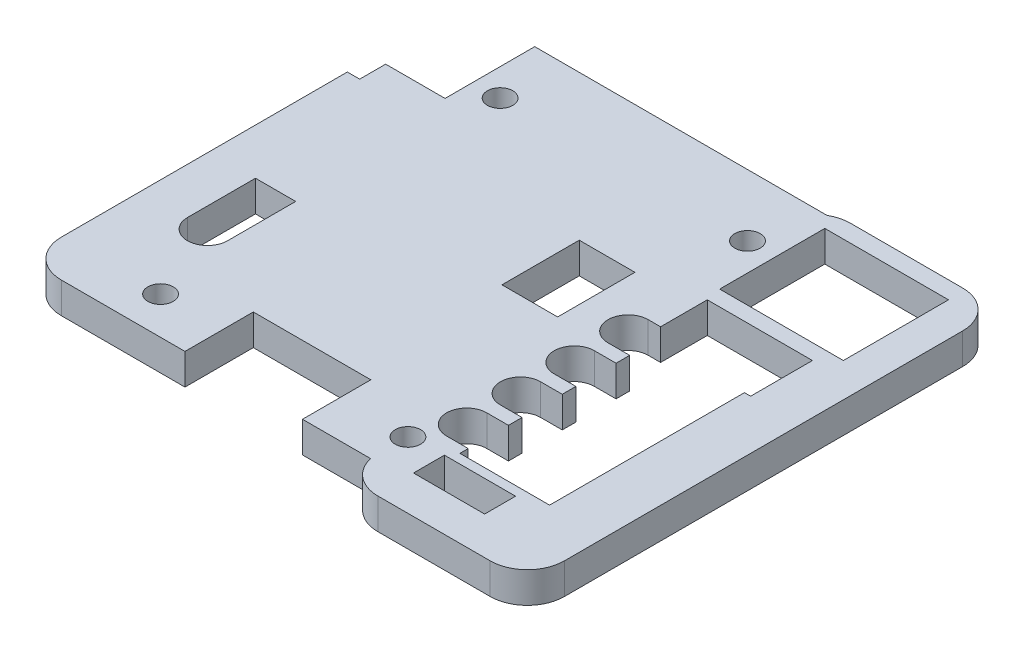
SolidWorks part; units mm, degrees
ref_plane "前视基准面" through (0, 0, 0) normal (0, 0, 1) x (1, 0, 0)
ref_plane "上视基准面" through (0, 0, 0) normal (0, 1, 0) x (1, 0, 0)
ref_plane "右视基准面" through (0, 0, 0) normal (1, 0, 0) x (0, 0, -1)
sketch "草图1" plane through (0, 0, 0) normal (0, 1, 0) x (1, 0, 0)
  line L0 (6, 0.3) -> (143.8, 0.3)
  line L1 (6, 0) -> (143.8, 0) construction
  line L2 (0, -6) -> (0, -68.8) construction
  line L3 (6, -74.8) -> (143.8, -74.8) construction
  line L4 (149.8, -6) -> (149.8, -68.8) construction
  line L5 (150.1, -6) -> (150.1, -68.8)
  line L6 (6, -75.1) -> (143.8, -75.1)
  line L7 (-0.3, -6) -> (-0.3, -68.8)
  arc A0 (143.8, 0) -> (149.8, -6) centre (143.8, -6) cw construction
  arc A1 (143.8, -74.8) -> (149.8, -68.8) centre (143.8, -68.8) ccw construction
  arc A2 (0, -68.8) -> (6, -74.8) centre (6, -68.8) ccw construction
  arc A3 (6, 0) -> (0, -6) centre (6, -6) ccw construction
  arc A4 (143.8, 0.3) -> (150.1, -6) centre (143.8, -6) cw
  arc A5 (143.8, -75.1) -> (150.1, -68.8) centre (143.8, -68.8) ccw
  arc A6 (-0.3, -68.8) -> (6, -75.1) centre (6, -68.8) ccw
  arc A7 (6, 0.3) -> (-0.3, -6) centre (6, -6) ccw
  point P7 (149.8, 0)
  point P12 (0, -74.8)
  point P15 (0, 0)
  dimension "D3" = 6
  dimension "D1" = 74.8
  dimension "D2" = 149.8
  dimension "D4" = 0.3
sketch "草图2" plane through (0, 0, 0) normal (0, -1, 0) x (-1, 0, 0)
  line L0 (-122.6, -55.35) -> (-108.9, -55.35) construction
  line L1 (-122.6, -69.85) -> (-108.9, -69.85) construction
  line L2 (-122.6, -69.85) -> (-122.6, -63.95) construction
  line L3 (-122.6, -63.95) -> (-108.9, -63.95) construction
  line L4 (-108.9, -69.85) -> (-108.9, -63.95) construction
  line L5 (-135.3, -1.25) -> (-35.3, -1.25) construction
  line L6 (-135.3, -1.25) -> (-135.3, -73.55) construction
  line L7 (-135.3, -73.55) -> (-35.3, -73.55) construction
  line L8 (-35.3, -1.25) -> (-35.3, -73.55) construction
  line L9 (-108.9, -61.25) -> (-108.9, -55.35) construction
  line L10 (-122.6, -61.25) -> (-108.9, -61.25) construction
  line L11 (-122.6, -61.25) -> (-122.6, -55.35) construction
  line L12 (-122.6, -46.75) -> (-108.9, -46.75) construction
  line L13 (-108.9, -52.65) -> (-108.9, -46.75) construction
  line L14 (-122.6, -52.65) -> (-108.9, -52.65) construction
  line L15 (-122.6, -52.65) -> (-122.6, -46.75) construction
  line L16 (-122.6, -38.15) -> (-108.9, -38.15) construction
  line L17 (-108.9, -44.05) -> (-108.9, -38.15) construction
  line L18 (-122.6, -44.05) -> (-108.9, -44.05) construction
  line L19 (-122.6, -44.05) -> (-122.6, -38.15) construction
  line L20 (0, -6) -> (0, -68.8) construction
  line L21 (-35.3, -73.55) -> (-0.8, -73.55) construction
  line L22 (-120.25, -26.65) -> (-111.25, -26.65) construction
  line L23 (-120.25, -26.65) -> (-120.25, -33.15) construction
  line L24 (-120.25, -33.15) -> (-111.25, -33.15) construction
  line L25 (-111.25, -26.65) -> (-111.25, -33.15) construction
  line L26 (-85.8, -48.75) -> (-81.1, -48.75) construction
  line L27 (-85.8, -48.75) -> (-85.8, -58.15) construction
  line L28 (-85.8, -58.15) -> (-81.1, -58.15) construction
  line L29 (-81.1, -48.75) -> (-81.1, -58.15) construction
  line L30 (-71.5, -48.65) -> (-68.2, -48.65) construction
  line L31 (-71.5, -48.65) -> (-71.5, -57.55) construction
  line L32 (-71.5, -57.55) -> (-68.2, -57.55) construction
  line L33 (-68.2, -48.65) -> (-68.2, -57.55) construction
  line L34 (-43.1, -45.05) -> (-38.6, -45.05) construction
  line L35 (-43.1, -45.05) -> (-43.1, -59.05) construction
  line L36 (-43.1, -59.05) -> (-38.6, -59.05) construction
  line L37 (-38.6, -45.05) -> (-38.6, -59.05) construction
  line L38 (-45.3, -61.55) -> (-40.8, -61.55) construction
  line L39 (-45.3, -61.55) -> (-45.3, -66.05) construction
  line L40 (-45.3, -66.05) -> (-40.8, -66.05) construction
  line L41 (-40.8, -61.55) -> (-40.8, -66.05) construction
  line L42 (-0.8, -73.55) -> (-0.8, -1.25) construction
  line L43 (-0.8, -1.25) -> (-35.3, -1.25) construction
  line L44 (-149.8, -6) -> (-149.8, -68.8) construction
  line L45 (-30.8, -34.65) -> (-27.3, -34.65) construction
  line L46 (-30.8, -34.65) -> (-30.8, -40.15) construction
  line L47 (-30.8, -40.15) -> (-27.3, -40.15) construction
  line L48 (-27.3, -34.65) -> (-27.3, -40.15) construction
  line L49 (-120.75, -33.65) -> (-110.75, -33.65)
  line L50 (-110.75, -26.15) -> (-110.75, -33.65)
  line L51 (-120.75, -26.15) -> (-110.75, -26.15)
  line L52 (-120.75, -26.15) -> (-120.75, -33.65)
  line L53 (-86.3, -48.25) -> (-86.3, -58.65)
  line L54 (-86.3, -58.65) -> (-80.6, -58.65)
  line L55 (-80.6, -48.25) -> (-80.6, -58.65)
  line L56 (-86.3, -48.25) -> (-80.6, -48.25)
  line L57 (-72, -48.15) -> (-72, -58.05)
  line L58 (-72, -58.05) -> (-67.7, -58.05)
  line L59 (-67.7, -48.15) -> (-67.7, -58.05)
  line L60 (-72, -48.15) -> (-67.7, -48.15)
  line L61 (-31.3, -34.15) -> (-31.3, -40.65)
  line L62 (-31.3, -40.65) -> (-26.8, -40.65)
  line L63 (-26.8, -34.15) -> (-26.8, -40.65)
  line L64 (-31.3, -34.15) -> (-26.8, -34.15)
  line L65 (-43.6, -44.55) -> (-43.6, -59.55)
  line L66 (-43.6, -59.55) -> (-38.1, -59.55)
  line L67 (-38.1, -44.55) -> (-38.1, -59.55)
  line L68 (-43.6, -44.55) -> (-38.1, -44.55)
  line L69 (-45.8, -61.05) -> (-45.8, -66.55)
  line L70 (-45.8, -66.55) -> (-40.3, -66.55)
  line L71 (-40.3, -61.05) -> (-40.3, -66.55)
  line L72 (-45.8, -61.05) -> (-40.3, -61.05)
  line L73 (-122.9, -44.35) -> (-108.6, -44.35)
  line L74 (-108.6, -44.35) -> (-108.6, -37.85)
  line L75 (-122.9, -37.85) -> (-108.6, -37.85)
  line L76 (-122.9, -44.35) -> (-122.9, -37.85)
  line L77 (-122.9, -52.95) -> (-108.6, -52.95)
  line L78 (-108.6, -52.95) -> (-108.6, -46.45)
  line L79 (-122.9, -46.45) -> (-108.6, -46.45)
  line L80 (-122.9, -52.95) -> (-122.9, -46.45)
  line L81 (-122.9, -61.55) -> (-108.6, -61.55)
  line L82 (-108.6, -61.55) -> (-108.6, -55.05)
  line L83 (-122.9, -55.05) -> (-108.6, -55.05)
  line L84 (-122.9, -61.55) -> (-122.9, -55.05)
  line L85 (-122.9, -70.15) -> (-108.6, -70.15)
  line L86 (-108.6, -70.15) -> (-108.6, -63.65)
  line L87 (-122.9, -63.65) -> (-108.6, -63.65)
  line L88 (-122.9, -70.15) -> (-122.9, -63.65)
  circle A0 centre (-103.2, -9.35) radius 1.65 construction
  circle A1 centre (-103.2, -64.25) radius 1.65 construction
  circle A2 centre (-63.2, -64.25) radius 1.65 construction
  circle A3 centre (-63.2, -9.35) radius 1.65 construction
  circle A4 centre (-130.8, -5.6) radius 1.25 construction
  circle A5 centre (-131.1, -55.65) radius 1.25 construction
  circle A6 centre (-47.7, -4.85) radius 1.25 construction
  circle A7 centre (-48.1, -68.75) radius 1.25 construction
  circle A8 centre (-22.8, -70.3) radius 1.25 construction
  circle A9 centre (-5.05, -71.05) radius 1.25 construction
  circle A10 centre (-5.05, -3.25) radius 1.25 construction
  circle A11 centre (-19, -37.4) radius 3.6 construction
  circle A12 centre (-103.2, -9.35) radius 2.05
  circle A13 centre (-63.2, -9.35) radius 2.05
  circle A14 centre (-63.2, -64.25) radius 2.05
  circle A15 centre (-103.2, -64.25) radius 2.05
  circle A16 centre (-19, -37.4) radius 4.1
  circle A17 centre (-130.8, -5.6) radius 1.75
  circle A18 centre (-131.1, -55.65) radius 1.75
  circle A19 centre (-48.1, -68.75) radius 1.75
  circle A20 centre (-22.8, -70.3) radius 1.75
  circle A21 centre (-5.05, -71.05) radius 1.75
  circle A22 centre (-5.05, -3.25) radius 1.75
  circle A23 centre (-47.7, -4.85) radius 1.75
  point P22 (0, -37.4)
  point P23 (-135.3, -37.4)
  point P28 (-115.75, -33.15)
  point P29 (-115.75, -38.15)
  point P30 (-111.25, -29.9)
  point P31 (-108.9, -41.1)
  point P79 (-0.8, -37.4)
  point P81 (-27.3, -37.4)
  dimension "D21" = 3.3
  dimension "D34" = 2.5
  dimension "D53" = 7.2
  dimension "D1" = 13.7
  dimension "D2" = 5.9
  dimension "D3" = 72.3
  dimension "D4" = 3.7
  dimension "D5" = 12.7
  dimension "D7" = 14.5
  dimension "D8" = 100
  dimension "D9" = 2.7
  dimension "D10" = 9
  dimension "D11" = 6.5
  dimension "D12" = 11.2
  dimension "D13" = 15.4
  dimension "D14" = 9.4
  dimension "D15" = 4.7
  dimension "D16" = 23.1
  dimension "D17" = 3.3
  dimension "D18" = 8.9
  dimension "D19" = 16
  dimension "D20" = 37.4
  dimension "D22" = 8.1
  dimension "D23" = 32.1
  dimension "D24" = 40
  dimension "D25" = 9.3
  dimension "D26" = 14
  dimension "D27" = 4.5
  dimension "D28" = 4.5
  dimension "D29" = 4.5
  dimension "D30" = 3.3
  dimension "D31" = 5.5
  dimension "D32" = 7.5
  dimension "D33" = 14.5
  dimension "D35" = 34.5
  dimension "D36" = 2
  dimension "D37" = 4.25
  dimension "D38" = 2.5
  dimension "D39" = 3.25
  dimension "D40" = 22
  dimension "D41" = 4.8
  dimension "D42" = 12.8
  dimension "D43" = 3.6
  dimension "D44" = 12.4
  dimension "D45" = 4.35
  dimension "D46" = 4.5
  dimension "D47" = 4.2
  dimension "D48" = 17.9
  dimension "D49" = 18.2
  dimension "D50" = 3.5
  dimension "D51" = 5.5
  dimension "D52" = 8.3
  dimension "D54" = 0.4
  dimension "D55" = 0.5
  dimension "D56" = 0.5
  dimension "D57" = 0.5
  dimension "D58" = 0.3
  dimension "D6" = 4
sketch "草图3" plane through (0, 0, 0) normal (0, 1, 0) x (1, 0, 0)
  line L0 (135.3, -1.25) -> (135.3, -73.55) construction
  line L1 (143.8, 0) -> (135.3, 0)
  line L2 (149.8, -6) -> (149.8, -68.8)
  line L3 (143.8, -74.8) -> (135.3, -74.8)
  line L4 (135.3, 0) -> (135.3, -74.8)
  line L5 (6, -74.8) -> (143.8, -74.8) construction
  arc A0 (143.8, 0) -> (149.8, -6) centre (143.8, -6) cw
  arc A1 (149.8, -68.8) -> (143.8, -74.8) centre (143.8, -68.8) cw
  point P17 (149.8, 0)
  dimension "D1" = 6
sketch "草图4" plane through (0, 0, 0) normal (0, 1, 0) x (1, 0, 0)
  line L0 (122.9, -62.85) -> (108.6, -62.85)
  line L1 (122.6, -63.15) -> (108.9, -63.15) construction
  line L2 (122.6, -63.15) -> (122.6, -70.65) construction
  line L3 (122.6, -70.65) -> (108.9, -70.65) construction
  line L4 (108.9, -63.15) -> (108.9, -70.65) construction
  line L5 (122.6, -69.85) -> (122.6, -63.95) construction
  line L6 (108.6, -62.85) -> (108.6, -70.95)
  line L7 (108.9, -69.85) -> (108.9, -63.95) construction
  line L8 (122.6, -54.55) -> (108.9, -54.55) construction
  line L9 (108.9, -54.55) -> (108.9, -62.05) construction
  line L10 (122.6, -62.05) -> (108.9, -62.05) construction
  line L11 (122.6, -54.55) -> (122.6, -62.05) construction
  line L12 (122.6, -45.95) -> (108.9, -45.95) construction
  line L13 (108.9, -45.95) -> (108.9, -53.45) construction
  line L14 (122.6, -53.45) -> (108.9, -53.45) construction
  line L15 (122.6, -45.95) -> (122.6, -53.45) construction
  line L16 (122.6, -37.35) -> (108.9, -37.35) construction
  line L17 (108.9, -37.35) -> (108.9, -44.85) construction
  line L18 (122.6, -44.85) -> (108.9, -44.85) construction
  line L19 (122.6, -37.35) -> (122.6, -44.85) construction
  line L20 (122.9, -70.95) -> (108.6, -70.95)
  line L21 (122.9, -62.85) -> (122.9, -70.95)
  line L22 (122.9, -54.25) -> (108.6, -54.25)
  line L23 (108.6, -54.25) -> (108.6, -62.35)
  line L24 (122.9, -62.35) -> (108.6, -62.35)
  line L25 (122.9, -54.25) -> (122.9, -62.35)
  line L26 (122.9, -45.65) -> (108.6, -45.65)
  line L27 (108.6, -45.65) -> (108.6, -53.75)
  line L28 (122.9, -53.75) -> (108.6, -53.75)
  line L29 (122.9, -45.65) -> (122.9, -53.75)
  line L30 (122.9, -37.05) -> (108.6, -37.05)
  line L31 (108.6, -37.05) -> (108.6, -45.15)
  line L32 (122.9, -45.15) -> (108.6, -45.15)
  line L33 (122.9, -37.05) -> (122.9, -45.15)
  point P11 (108.9, -66.9)
  point P12 (108.9, -66.9)
  dimension "D1" = 7.5
  dimension "D3" = 1.1
  dimension "D4" = 0.3
  dimension "D2" = 4
extrude "拉伸-薄壁1" add sketch "草图2" along normal blind 5 thin contours A13 | A12 | A14 | A15 thin type one direction wall 4
sketch "草图6" plane through (0, 0, 0) normal (0, 1, 0) x (1, 0, 0)
  line L0 (127.2, 1.45) -> (109.0462, 1.45)
  line L1 (133.2, -4.55) -> (133.2, -68.95)
  line L2 (127.2, -74.95) -> (109.0462, -74.95)
  line L3 (33.4345, -36.75) -> (43.3021, -36.75) construction
  line L4 (63.2, 0.65) -> (106.0528, 0.65)
  line L6 (63.2, 0.65) -> (49.7, 0.65)
  line L10 (122.9, -70.95) -> (108.6, -70.95) construction
  line L11 (108.6, -62.85) -> (108.6, -70.95) construction
  line L12 (47.2, -1.85) -> (47.2, -64.3)
  line L13 (103.2, -70.3) -> (53.2, -70.3)
  circle A1 centre (103.2, -64.25) radius 6.05 construction
  arc A3 (133.2, -4.55) -> (127.2, 1.45) centre (127.2, -4.55) ccw
  arc A4 (109.0462, -74.95) -> (103.2, -70.3) centre (109.0462, -68.95) cw
  circle A5 centre (63.2, -64.25) radius 6.05 construction
  arc A6 (133.2, -68.95) -> (127.2, -74.95) centre (127.2, -68.95) cw
  arc A7 (109.0462, 1.45) -> (106.0528, 0.65) centre (109.0462, -4.55) ccw
  arc A9 (47.2, -64.3) -> (53.2, -70.3) centre (53.2, -64.3) ccw
  circle A10 centre (103.2, -9.35) radius 2.05 construction
  circle A11 centre (103.2, -64.25) radius 2.05 construction
  circle A12 centre (63.2, -64.25) radius 2.05 construction
  circle A13 centre (103.2, -9.35) radius 2.05
  circle A14 centre (103.2, -64.25) radius 2.05
  circle A15 centre (63.2, -64.25) radius 2.05
  circle A16 centre (63.2, -9.35) radius 2.05 construction
  circle A17 centre (63.2, -9.35) radius 2.05
  arc A18 (49.7, 0.65) -> (47.2, -1.85) centre (49.7, -1.85) ccw
  point P37 (105.6, -74.95)
  point P42 (130.9, -6.15)
  dimension "D6" = 6
  dimension "D7" = 5
  dimension "D8" = 6
  dimension "D9" = 6
  dimension "D10" = 6
  dimension "D11" = 6
  dimension "D2" = 27.5
  dimension "D3" = 4
  dimension "D4" = 3
  dimension "D5" = 16
  dimension "D12" = 30
  dimension "D13" = 10
extrude "凸台-拉伸1" add sketch "草图6" against normal up to surface (5 mm away) up to face at (97.15, -5, 9.35)
sketch "草图7" plane through (0, -5, 3) normal (0, -1, 0) x (1, 0, 0)
  line L9 (80.466, 15.85) -> (96.6871, 15.85) construction
  line L43 (107.2, -14.628) -> (107.2, -27.7853) construction
  line L44 (108.9, 22) -> (108.9, 67) construction
  line L45 (122.6, 67) -> (108.9, 67) construction
  line L46 (122.6, 22) -> (122.6, 67) construction
  line L47 (122.6, 22) -> (108.9, 22) construction
  line L48 (120.2, 9.55) -> (113.2, 9.55)
  line L49 (120.2, 4.55) -> (120.2, 9.55)
  line L50 (113.2, 4.55) -> (120.2, 4.55)
  line L51 (113.2, 9.55) -> (113.2, 4.55)
  line L52 (80.4, 48.65) -> (80.4, 33.65)
  line L53 (85.4, 48.65) -> (80.4, 48.65)
  line L54 (97.9, 36.55) -> (89.9, 36.55)
  line L55 (97.9, 25.55) -> (97.9, 36.55)
  line L56 (89.9, 25.55) -> (97.9, 25.55)
  line L57 (89.9, 36.55) -> (89.9, 25.55)
  line L58 (66.4, 33.65) -> (80.4, 33.65)
  line L59 (50.4, 54.65) -> (50.4, 33.65)
  line L60 (85.4, 54.65) -> (50.4, 54.65)
  line L61 (85.4, 48.65) -> (85.4, 54.65)
  line L62 (47.4, 10.15) -> (66.4, 10.15)
  line L63 (47.4, 33.65) -> (47.4, 10.15)
  line L64 (50.4, 33.65) -> (47.4, 33.65)
  line L65 (66.4, 10.15) -> (66.4, 15.35)
  line L66 (66.4, 24.35) -> (72.4, 24.35)
  line L67 (66.4, 24.35) -> (66.4, 33.65)
  line L68 (72.4, 15.35) -> (66.4, 15.35)
  line L69 (122.9, 21.7) -> (122.9, 67.3)
  line L70 (122.9, 67.3) -> (108.6, 67.3)
  line L71 (72.4, 24.35) -> (72.4, 15.35)
  line L72 (92.2, 15.35) -> (75.2, 15.35)
  line L73 (92.2, 23.55) -> (92.2, 15.35)
  line L74 (75.2, 23.55) -> (92.2, 23.55)
  line L75 (107.7, 23.55) -> (107.7, 15.35)
  line L76 (98.2, 23.55) -> (107.7, 23.55)
  line L77 (98.2, 15.35) -> (98.2, 23.55)
  line L78 (107.7, 15.35) -> (98.2, 15.35)
  line L79 (75.2, 15.35) -> (75.2, 23.55)
  line L80 (108.6, 21.7) -> (108.6, 67.3)
  line L81 (122.9, 21.7) -> (108.6, 21.7)
  circle A0 centre (103.2, 61.25) radius 2.05 construction
  circle A1 centre (103.2, 61.25) radius 2.05
  circle A5 centre (59.2, 61.25) radius 2.05
  circle A6 centre (103.2, 61.25) radius 2.05
extrude "切除-拉伸1" [suppressed] cut sketch "草图7" against normal blind 5 contours L81 L69 L70 L80 | L78 L75 L76 L77 | L54 L57 L56 L55 | L79 L72 L73 L74 | L71 L66 L67 L58 L52 L53 L61 L60 L59 L64 L63 L62 L65 L68
sketch "草图8" plane through (0, 0, 0) normal (0, -1, 0) x (1, 0, 0)
  line L3 (106.2, 28.95) -> (106.2, 55.65) construction
  line L6 (133.2, 68.95) -> (133.2, 4.55) construction
  line L7 (109.0462, 74.95) -> (127.2, 74.95) construction
  line L9 (80.466, -18.85) -> (96.6871, -18.85) construction
  line L10 (107.2, 11.628) -> (107.2, 24.7853) construction
  line L14 (5.1637, 36.85) -> (19.0276, 36.85) construction
  line L15 (106.2, 60.7) -> (109.7, 60.7)
  line L18 (63.2, 64.25) -> (46.0308, 64.25) construction
  line L19 (67.2, 40.45) -> (49.2, 40.45)
  line L20 (106.2, 54.2) -> (109.7, 54.2)
  line L22 (67.2, 13.45) -> (67.2, 40.45)
  line L23 (49.2, 13.45) -> (67.2, 13.45)
  line L24 (49.2, 40.45) -> (49.2, 13.45)
  line L25 (98.5, 35.95) -> (89.5, 35.95)
  line L26 (98.5, 23.45) -> (98.5, 35.95)
  line L27 (89.5, 23.45) -> (98.5, 23.45)
  line L28 (89.5, 35.95) -> (89.5, 23.45)
  line L29 (108.2, 30.95) -> (125.2, 30.95) construction
  line L30 (128.2, 18.45) -> (108.2, 18.45)
  line L31 (128.2, 2.45) -> (128.2, 18.45)
  line L32 (108.2, 2.45) -> (128.2, 2.45)
  line L37 (108.2, 18.45) -> (108.2, 2.45)
  line L38 (125.2, 20.95) -> (125.2, 30.95)
  line L47 (125.2, 30.95) -> (124.2, 30.95)
  line L48 (108.2, 30.95) -> (108.2, 20.95)
  line L49 (108.2, 30.95) -> (109.7, 30.95)
  line L50 (125.2, 20.95) -> (108.2, 20.95)
  line L51 (111.7, 64.75) -> (122.2, 64.75)
  line L52 (122.2, 62.75) -> (122.2, 69.95)
  line L53 (124.2, 30.95) -> (124.2, 63.75)
  line L54 (109.7, 63.75) -> (124.2, 63.75)
  line L55 (111.7, 69.95) -> (122.2, 69.95)
  line L56 (111.7, 69.95) -> (111.7, 62.75)
  line L57 (109.7, 30.95) -> (109.7, 63.75)
  line L58 (75.2, 64.35) -> (89.2, 64.35)
  line L59 (75.2, 73.35) -> (75.2, 64.35)
  line L60 (89.2, 73.35) -> (75.2, 73.35)
  line L61 (89.2, 64.35) -> (89.2, 73.35)
  line L62 (106.2, 51.8) -> (109.7, 51.8)
  line L63 (106.2, 45.3) -> (109.7, 45.3)
  line L64 (106.2, 42.9) -> (109.7, 42.9)
  line L65 (106.2, 36.4) -> (109.7, 36.4)
  line L66 (106.2, 34) -> (109.7, 34)
  line L67 (106.2, 27.5) -> (108.2, 27.5)
  line L68 (109.7, 34) -> (109.7, 27.5)
  line L69 (109.7, 27.5) -> (108.2, 27.5)
  line L70 (109.7, 36.4) -> (109.7, 42.9)
  line L71 (109.7, 45.3) -> (109.7, 51.8)
  line L72 (109.7, 54.2) -> (109.7, 60.7)
  circle A1 centre (57.9, 42.45) radius 3.25
  circle A2 centre (103.2, 9.35) radius 2.4
  circle A3 centre (106.2, 57.45) radius 3.25
  circle A4 centre (63.2, 9.35) radius 2.4
  circle A5 centre (103.2, 64.25) radius 2.4 construction
  circle A10 centre (106.2, 48.55) radius 3.25
  circle A11 centre (63.2, 64.25) radius 2.4 construction
  circle A14 centre (106.2, 39.65) radius 3.25
  circle A15 centre (106.2, 30.75) radius 3.25
  dimension "D7" = 27.5
  dimension "D1" = 10
  dimension "D3" = 8.9
  dimension "D2" = 27
  dimension "D4" = 8.9
  dimension "D5" = 8.9
  dimension "D6" = 17.5
  dimension "D8" = 20
extrude "切除-拉伸2" [suppressed] cut sketch "草图8" along normal through all
sketch "草图10" plane through (0, 0, 0) normal (0, -1, 0) x (1, 0, 0)
  line L0 (67.2, 40.45) -> (49.2, 40.45)
  line L1 (49.2, 40.45) -> (49.2, 13.45)
  line L2 (49.2, 13.45) -> (67.2, 13.45)
  line L3 (67.2, 13.45) -> (67.2, 40.45)
sketch "草图9" plane through (0, -5, 0) normal (0, -1, 0) x (1, 0, 0)
  line L0 (58.8, 13.85) -> (58.8, 1.85)
  line L2 (58.8, 1.85) -> (45.8, 1.85)
  line L3 (45.8, 1.85) -> (45.8, 13.85)
  line L4 (45.8, 13.85) -> (58.8, 13.85)
  circle A0 centre (63.2, 9.35) radius 2.05 construction
  circle A1 centre (63.2, 9.35) radius 2.05 construction
  dimension "D1" = 13
  dimension "D2" = 4.5
  dimension "D3" = 4.4
  dimension "D4" = 12
extrude "切除-拉伸3" [suppressed] cut sketch "草图9" against normal through all
extrude "切除-拉伸5_电源模块(一般不用，焊接模块时才需要)" [suppressed] cut sketch "草图10" along normal blind 2
sketch "草图11" plane through (0, -5, 5) normal (0, -1, 0) x (1, 0, 0)
  line L3 (106.0528, -5.65) -> (49.7, -5.65) construction
  line L9 (80.466, -18.85) -> (96.6871, -18.85) construction
  line L10 (107.2, 11.628) -> (107.2, 24.7853) construction
  line L19 (106.2, -55.55) -> (106.2, -28.85) construction
  line L54 (63.2, 4.35) -> (46.0308, 4.35) construction
  line L55 (108.2, 25.85) -> (125.2, 25.85) construction
  line L56 (45.8, 13.05) -> (49.2, 13.05)
  line L57 (45.8, 13.05) -> (45.8, 6.35)
  line L58 (39.8, 13.05) -> (45.8, 13.05)
  line L59 (39.8, 6.35) -> (39.8, 13.05)
  line L60 (45.8, 6.35) -> (39.8, 6.35)
  line L61 (45.8, -3.15) -> (58.8, -3.15)
  line L62 (45.8, 8.85) -> (45.8, -3.15)
  line L63 (73.2, 54.25) -> (92.2, 54.25)
  line L64 (73.2, 66.25) -> (73.2, 54.25)
  line L65 (92.2, 66.25) -> (73.2, 66.25)
  line L66 (92.2, 54.25) -> (92.2, 66.25)
  line L67 (127.7, 13.35) -> (107.7, 13.35)
  line L68 (127.7, -3.65) -> (127.7, 13.35)
  line L69 (107.7, -3.65) -> (127.7, -3.65)
  line L70 (107.7, 13.35) -> (107.7, -3.65)
  line L71 (58.8, 8.85) -> (45.8, 8.85)
  line L72 (58.8, -3.15) -> (58.8, 8.85)
  line L73 (98.5, 30.35) -> (89.5, 30.35)
  line L74 (98.5, 17.85) -> (98.5, 30.35)
  line L75 (89.5, 17.85) -> (98.5, 17.85)
  line L76 (89.5, 30.35) -> (89.5, 17.85)
  line L77 (61.15, 46.35) -> (61.15, 35.35)
  line L78 (54.65, 46.35) -> (54.65, 35.35)
  line L79 (106.2, 56) -> (109.7, 56)
  line L80 (106.2, 49.5) -> (109.7, 49.5)
  line L81 (106.2, 47.3) -> (109.7, 47.3)
  line L82 (106.2, 40.8) -> (109.7, 40.8)
  line L83 (109.7, 38.6) -> (106.2, 38.6)
  line L84 (109.7, 32.1) -> (109.7, 38.6)
  line L85 (106.2, 32.1) -> (109.7, 32.1)
  line L86 (106.2, 29.9) -> (109.7, 29.9)
  line L87 (106.2, 23.4) -> (108.2, 23.4)
  line L88 (125.2, 15.85) -> (125.2, 25.85)
  line L89 (108.7, 58.85) -> (120.2, 58.85)
  line L90 (67.2, 35.35) -> (49.2, 35.35)
  line L91 (67.2, 8.35) -> (67.2, 35.35)
  line L92 (120.2, 57.35) -> (120.2, 63.85)
  line L93 (124.2, 57.35) -> (120.2, 57.35)
  line L94 (124.2, 25.85) -> (124.2, 57.35)
  line L95 (125.2, 25.85) -> (124.2, 25.85)
  line L96 (49.2, 8.35) -> (67.2, 8.35)
  line L97 (109.7, 57.35) -> (124.2, 57.35)
  line L98 (108.7, 63.85) -> (120.2, 63.85)
  line L99 (108.2, 25.85) -> (108.2, 15.85)
  line L100 (49.2, 35.35) -> (49.2, 8.35)
  line L101 (108.7, 63.85) -> (108.7, 57.35)
  line L102 (109.7, 25.85) -> (109.7, 57.35)
  line L103 (108.2, 25.85) -> (109.7, 25.85)
  line L104 (125.2, 15.85) -> (108.2, 15.85)
  circle A13 centre (63.2, 4.35) radius 2.4 construction
  circle A14 centre (103.2, 4.35) radius 2.4 construction
  circle A15 centre (57.9, 46.35) radius 3.25
  circle A16 centre (106.2, 52.75) radius 3.25
  circle A17 centre (106.2, 44.05) radius 3.25
  circle A18 centre (106.2, 35.35) radius 3.25
  circle A19 centre (106.2, 26.65) radius 3.25
  circle A20 centre (63.2, 59.25) radius 2.4
  circle A21 centre (103.2, 59.25) radius 2.4
  dimension "D1" = 52
extrude "切除-拉伸4" cut sketch "草图11" against normal through all contours L98 L101 L89 L92 | L79 A16 L80 L102 | L81 A17 L82 L102 | L83 A18 L85 L84 | L86 A19 L103 L102 | L99 A19 L87 | L100 L56 L57 L71 | L77 A15 L78 L90 | L63 L66 L65 L64 | L97 L102 L103 L99 L104 L88 L95 L94 | A16 | A17 | A18 | A19 | L74 L73 L76 L75 | L67 L70 L69 L68 | A15 | L72 L71 L62 L61 | L57 L60 L59 L58 region at (47.5, -5, 15.95) region at (57.9, -5, 44.6049) region at (114.45, -5, 66.35) region at (107.95, -5, 60.9262) region at (109.6262, -5, 49.05) region at (109.6262, -5, 40.35) region at (108.9903, -5, 33.7511) region at (107.7112, -5, 28.6021)
sketch "草图12" plane through (0, -5, 0) normal (0, -1, 0) x (1, 0, 0)
  line L0 (58.8, 1.85) -> (58.8, -0.65)
  line L1 (106.0528, -0.65) -> (45.7, -0.65) construction
  line L2 (43.2, 1.85) -> (43.2, 11.35) construction
  line L3 (45.8, 11.35) -> (43.2, 11.35) construction
  line L4 (45.8, 11.35) -> (45.8, 1.85) construction
  line L5 (45.8, 1.85) -> (58.8, 1.85) construction
  line L6 (106.0528, -0.65) -> (45.7, -0.65)
  line L7 (43.2, 1.85) -> (43.2, 11.35)
  line L8 (45.8, 11.35) -> (43.2, 11.35)
  line L9 (45.8, 11.35) -> (45.8, 1.85)
  line L10 (45.8, 1.85) -> (58.8, 1.85)
  arc A0 (43.2, 1.85) -> (45.7, -0.65) centre (45.7, 1.85) ccw construction
  arc A1 (43.2, 1.85) -> (45.7, -0.65) centre (45.7, 1.85) ccw
extrude "切除-拉伸5" cut sketch "草图12" against normal through all contours L7 A1 L6 L0 L10 L9 L8 region at (58.6032, -5, 0.6)
equation "\"D1@草图3\"=\"D3@草图1\""
